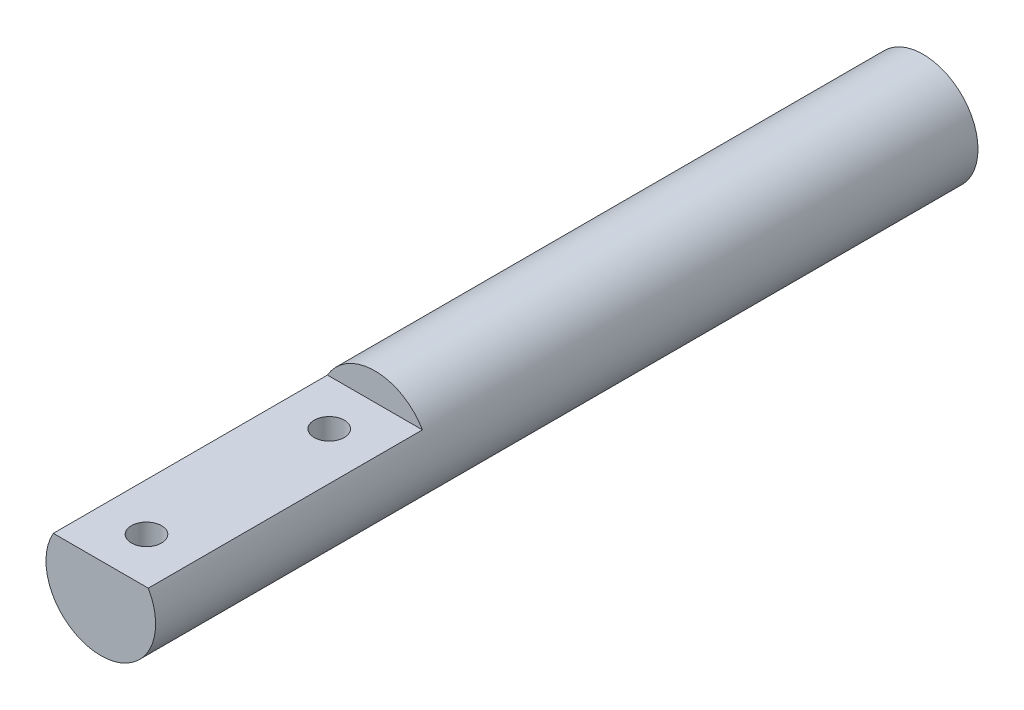
SolidWorks part; units mm, degrees
ref_plane "Plan de face" through (0, 0, 0) normal (0, 0, 1) x (1, 0, 0)
ref_plane "Plan de dessus" through (0, 0, 0) normal (0, 1, 0) x (1, 0, 0)
ref_plane "Plan de droite" through (0, 0, 0) normal (1, 0, 0) x (0, 0, -1)
sketch "Esquisse1" plane through (0, 0, 0) normal (0, 0, 1) x (1, 0, 0)
  circle A0 centre (0, 0) radius 6
  dimension "D1" = 12
extrude "Boss.-Extru.1" add sketch "Esquisse1" along normal blind 90
sketch "Esquisse2" plane through (0, 0, 90) normal (0, 0, 1) x (1, 0, 0)
  line L0 (-5.1962, 3) -> (5.1962, 3)
  line L1 (0, 0) -> (0, 3) construction
  line L2 (-5.1962, 3) -> (-5.1962, 9)
  line L3 (-5.1962, 9) -> (5.1962, 9)
  line L4 (0, 9) -> (0, 3) construction
  line L5 (5.1962, 3) -> (5.1962, 9)
  circle A0 centre (0, 0) radius 6 construction
  dimension "D1" = 3
  dimension "D2" = 6
extrude "Enlèv. mat.-Extru.1" cut sketch "Esquisse2" against normal blind 30
sketch "Esquisse3" plane through (0, 3, 0) normal (0, 1, 0) x (1, 0, 0)
  line L0 (0, -56.9549) -> (0, -90) construction
  line L1 (-5.1962, -90) -> (5.1962, -90) construction
  circle A0 centre (0, -85) radius 1.65
  circle A1 centre (0, -65) radius 1.65
  dimension "D1" = 20
  dimension "D2" = 5
  dimension "D3" = 3.3
extrude "Enlèv. mat.-Extru.2" cut sketch "Esquisse3" against normal through all
